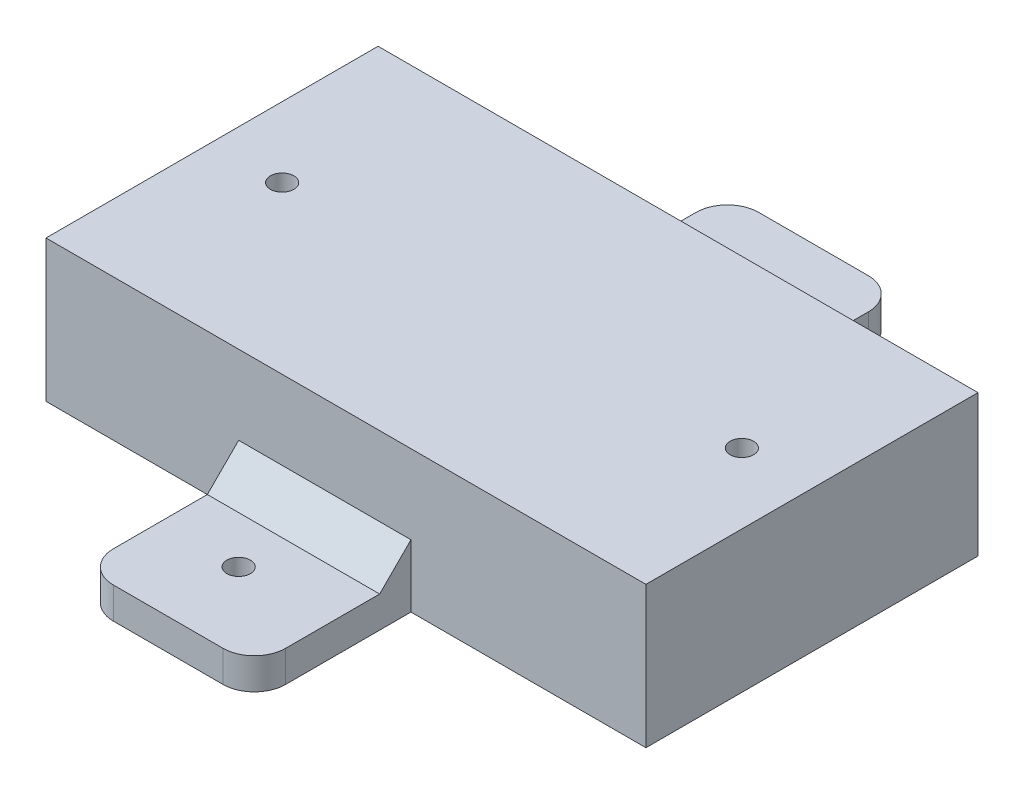
SolidWorks part; units mm, degrees
ref_plane "Спереди" through (0, 0, 0) normal (0, 0, 1) x (1, 0, 0)
ref_plane "Сверху" through (0, 0, 0) normal (0, 1, 0) x (1, 0, 0)
ref_plane "Справа" through (0, 0, 0) normal (1, 0, 0) x (0, 0, -1)
other "Configuration Table"
sketch "Эскиз1" plane through (0, 0, 0) normal (0, 1, 0) x (1, 0, 0)
  line L1 (-38.3, -21.2) -> (38.3, -21.2)
  line L2 (-38.3, -21.2) -> (-38.3, 21.2)
  line L3 (-38.3, 21.2) -> (38.3, 21.2)
  line L4 (38.3, -21.2) -> (38.3, 21.2)
  line L5 (-38.3, -21.2) -> (38.3, 21.2) construction
  line L6 (-38.3, 21.2) -> (38.3, -21.2) construction
  point P0 (0, 0)
  dimension "D1" = 76.6
  dimension "D2" = 42.4
extrude "Бобышка-Вытянуть1" add sketch "Эскиз1" along normal blind 18.07
sketch "Эскиз2" plane through (0, 18.07, 0) normal (0, 1, 0) x (1, 0, 0)
  line L0 (0, 0) -> (58.7, 0) construction
  line L1 (0, 0) -> (0, 38.349) construction
  line L2 (38.3, -21.2) -> (38.3, 21.2) construction
  circle A0 centre (29.35, 0) radius 1.5
  circle A1 centre (-29.35, 0) radius 1.5
  point P6 (30.85, 0)
  dimension "D2" = 3
  dimension "D1" = 7.45
extrude "Вырез-Вытянуть1" cut sketch "Эскиз2" against normal blind 10
sketch "Эскиз4" plane through (0, 0, 0) normal (0, -1, 0) x (1, 0, 0)
  line L0 (-38.3, 21.2) -> (38.3, 21.2) construction
  line L1 (8.3, 21.2) -> (-13.7, 21.2)
  line L2 (8.3, 21.2) -> (8.3, 37.2)
  line L3 (4.3, 41.2) -> (-9.7, 41.2)
  line L4 (-13.7, 21.2) -> (-13.7, 37.2)
  line L5 (38.3, 21.2) -> (38.3, -21.2) construction
  line L6 (0, 0) -> (58.0491, 0) construction
  line L7 (4.3, -41.2) -> (-9.7, -41.2)
  line L8 (-13.7, -21.2) -> (-13.7, -37.2)
  line L9 (8.3, -21.2) -> (-13.7, -21.2)
  line L10 (8.3, -21.2) -> (8.3, -37.2)
  circle A0 centre (-3.7, 31.2) radius 1.5
  circle A1 centre (-3.7, -31.2) radius 1.5
  arc A2 (-13.7, 37.2) -> (-9.7, 41.2) centre (-9.7, 37.2) cw
  arc A3 (8.3, 37.2) -> (4.3, 41.2) centre (4.3, 37.2) ccw
  arc A4 (-9.7, -41.2) -> (-13.7, -37.2) centre (-9.7, -37.2) cw
  arc A5 (4.3, -41.2) -> (8.3, -37.2) centre (4.3, -37.2) ccw
  point P21 (-13.7, 41.2)
  point P24 (8.3, 41.2)
  point P27 (-13.7, -41.2)
  point P30 (8.3, -41.2)
  dimension "D4" = 3
  dimension "D7" = 4
  dimension "D8" = 4
  dimension "D9" = 4
  dimension "D10" = 4
  dimension "D1" = 22
  dimension "D2" = 20
  dimension "D3" = 30
  dimension "D5" = 10
  dimension "D6" = 10
extrude "Бобышка-Вытянуть2" add sketch "Эскиз4" against normal blind 4
chamfer "Фаска1" distance 4 angle 45 2 edges at (-2.7, 4, -21.2) (-2.7, 4, 21.2)
